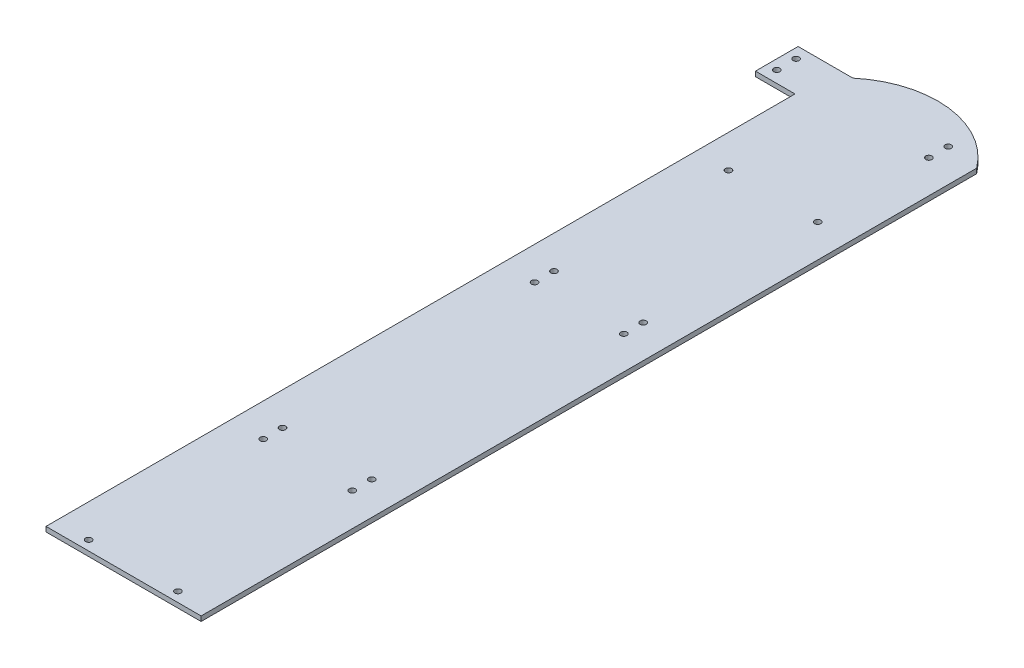
SolidWorks part; units mm, degrees
ref_plane "Front Plane" through (0, 0, 0) normal (0, 0, 1) x (1, 0, 0)
ref_plane "Top Plane" through (0, 0, 0) normal (0, 1, 0) x (1, 0, 0)
ref_plane "Right Plane" through (0, 0, 0) normal (1, 0, 0) x (0, 0, -1)
sketch "Sketch1" plane through (0, 0, 0) normal (0, 1, 0) x (1, 0, 0)
  line L2 (0, 0) -> (0, -508)
  line L3 (0, -508) -> (101.6, -508)
  line L4 (101.6, 0) -> (101.6, -508)
  arc A0 (0, 0) -> (101.6, 0) centre (50.8, -38.1) cw
  dimension "D3" = 63.5
  dimension "D1" = 508
  dimension "D2" = 101.6
extrude "Boss-Extrude1" add sketch "Sketch1" along normal blind 3.175
sketch "Sketch2" plane through (0, 0, 0) normal (0, -1, 0) x (1, 0, 0)
  line L0 (21.59, 82.55) -> (80.01, 82.55) construction
  line L1 (0, 508) -> (101.6, 508) construction
  circle A0 centre (21.59, 501.65) radius 2.032
  circle A1 centre (80.01, 501.65) radius 2.032
  circle A2 centre (21.59, 82.55) radius 2.032
  circle A3 centre (80.01, 82.55) radius 2.032
  arc A4 (0, 0) -> (101.6, 0) centre (50.8, 38.1) ccw construction
  circle A5 centre (21.59, 209.55) radius 2.032
  circle A6 centre (80.01, 209.55) radius 2.032
  circle A7 centre (21.59, 196.85) radius 2.032
  circle A8 centre (80.01, 196.85) radius 2.032
  circle A9 centre (21.59, 374.65) radius 2.032
  circle A10 centre (80.01, 374.65) radius 2.032
  circle A11 centre (21.59, 387.35) radius 2.032
  circle A12 centre (80.01, 387.35) radius 2.032
  point P11 (50.8, -25.4)
  point P12 (50.8, 82.55)
  dimension "D1" = 4.064
  dimension "D2" = 58.42
  dimension "D3" = 6.35
  dimension "D4" = 419.1
  dimension "D5" = 114.3
  dimension "D6" = 177.8
  dimension "D7" = 12.7
  dimension "D8" = 12.7
extrude "Cut-Extrude1" cut sketch "Sketch2" against normal through all
sketch "Sketch3" plane through (0, 3.175, 0) normal (0, 1, 0) x (1, 0, 0)
  line L0 (0, 0) -> (0, -508) construction
  line L1 (-30.48, 10.541) -> (20.32, 10.541)
  line L2 (-30.48, 10.541) -> (-30.48, -22.2585)
  line L3 (-30.48, -22.2585) -> (20.32, -22.2585)
  line L4 (20.32, 10.541) -> (20.32, -22.2585)
  dimension "D1" = 32.7995
  dimension "D2" = 50.8
  dimension "D3" = 30.48
  dimension "D4" = 22.2585
extrude "Boss-Extrude4" add sketch "Sketch3" against normal up to surface (3.175 mm away) up to face at (80.01, 0, 207.518)
sketch "Sketch6" plane through (0, 3.175, 0) normal (0, 1, 0) x (1, 0, 0)
  line L0 (101.6, -508) -> (101.6, 0) construction
  line L1 (0, -508) -> (101.6, -508) construction
  circle A0 centre (-19.558, 2.921) radius 2.032
  circle A1 centre (-19.558, -9.779) radius 2.032
  circle A2 centre (80.01, 2.921) radius 2.032
  circle A3 centre (80.01, -9.779) radius 2.032
  dimension "D1" = 4.064
  dimension "D2" = 21.59
  dimension "D3" = 99.568
  dimension "D4" = 12.7
  dimension "D5" = 498.221
extrude "Cut-Extrude4" cut sketch "Sketch6" against normal through all
sketch "Sketch7" plane through (0, 3.175, 0) normal (0, 1, 0) x (1, 0, 0)
  line L0 (-30.48, 10.541) -> (-30.48, -22.2585) construction
  line L1 (0, -22.2585) -> (-30.48, -22.2585)
  line L2 (0, -22.2585) -> (0, -17.399)
  line L3 (0, -17.399) -> (-30.48, -17.399)
  line L4 (-30.48, -22.2585) -> (-30.48, -17.399)
  line L6 (-30.48, 10.541) -> (-27.178, 10.541)
  line L7 (-30.48, 10.541) -> (-30.48, -17.399)
  line L8 (-30.48, -17.399) -> (-27.178, -17.399)
  line L9 (-27.178, 10.541) -> (-27.178, -17.399)
  line M8 (9.9797, 10.541) -> (-30.48, 10.541)
  line M9 (-30.48, 10.541) -> (-30.48, -22.2585)
  line M10 (-30.48, -22.2585) -> (0, -22.2585)
  dimension "D1" = 4.8595
  dimension "D2" = 3.302
extrude "Cut-Extrude5" cut sketch "Sketch7" against normal through all contours L2 L3 M9 M10 | L9 L3 M8 M9 region at (-15.24, 3.175, 19.8288) region at (-28.829, 3.175, 3.429)
sketch "Sketch8" plane through (0, 3.175, 0) normal (0, 1, 0) x (1, 0, 0)
  line L0 (0, -17.399) -> (-27.178, -17.399) construction
  line L1 (-27.178, 10.541) -> (-25.908, 10.541)
  line L2 (-27.178, 10.541) -> (-27.178, -17.399)
  line L3 (-27.178, -17.399) -> (-25.908, -17.399)
  line L4 (-25.908, 10.541) -> (-25.908, -17.399)
  dimension "D1" = 1.27
extrude "Cut-Extrude6" cut sketch "Sketch8" against normal through all
